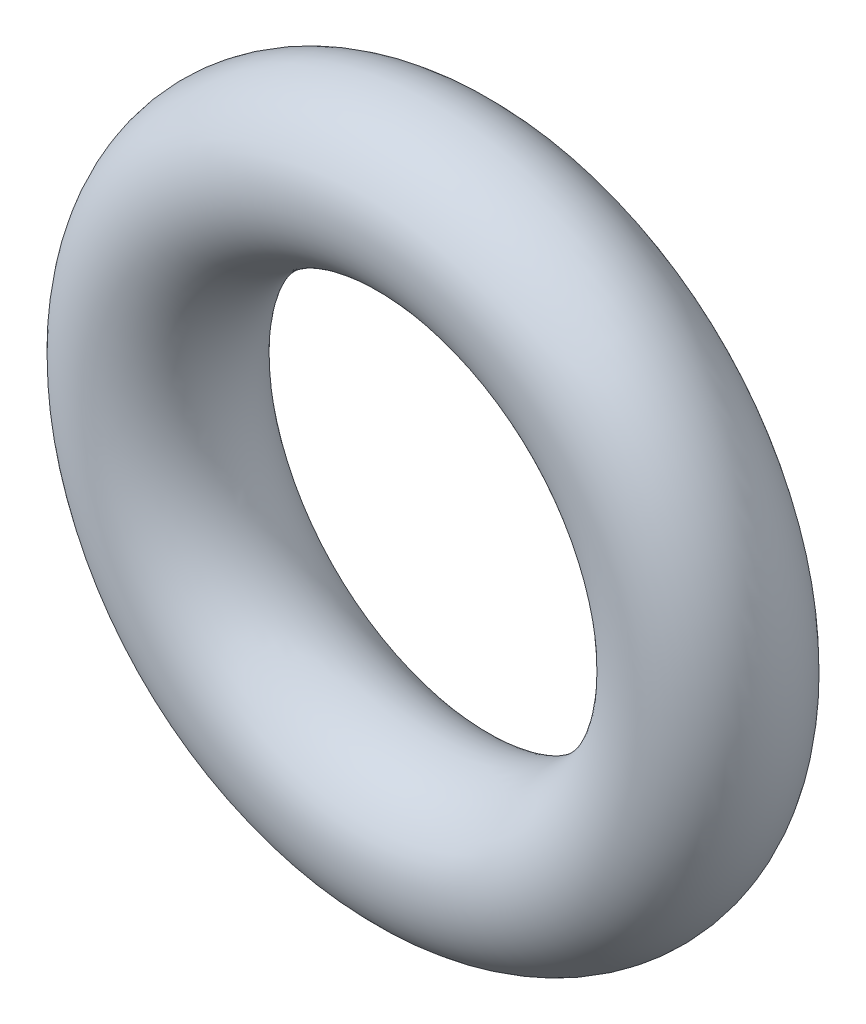
SolidWorks part; units mm, degrees
ref_plane "Front" through (0, 0, 0) normal (0, 0, 1) x (1, 0, 0)
ref_plane "Top" through (0, 0, 0) normal (0, 1, 0) x (1, 0, 0)
ref_plane "Right" through (0, 0, 0) normal (1, 0, 0) x (0, 0, -1)
sketch "Sketch1" plane through (0, 0, 0) normal (1, 0, 0) x (0, -1, 0)
  line L0 (0, -0.5) -> (0, 0.5) construction
  line L2 (-2.475, 0) -> (2.475, 0) construction
  line L3 (-1.25, 0) -> (1.25, 0) construction
  circle A0 centre (1.75, 0) radius 0.5
  point P9 (1.25, 0)
  point P10 (2.25, 0)
  point P13 (1.75, 0.5)
  point P14 (1.75, -0.5)
  dimension "Width" = 1
  dimension "ID" = 2.5
revolve "Revolve1" add sketch "Sketch1" angle 360 about L0
ref_axis "Axis1" through (0, 0, -0.55) along (0, 0, 1)
